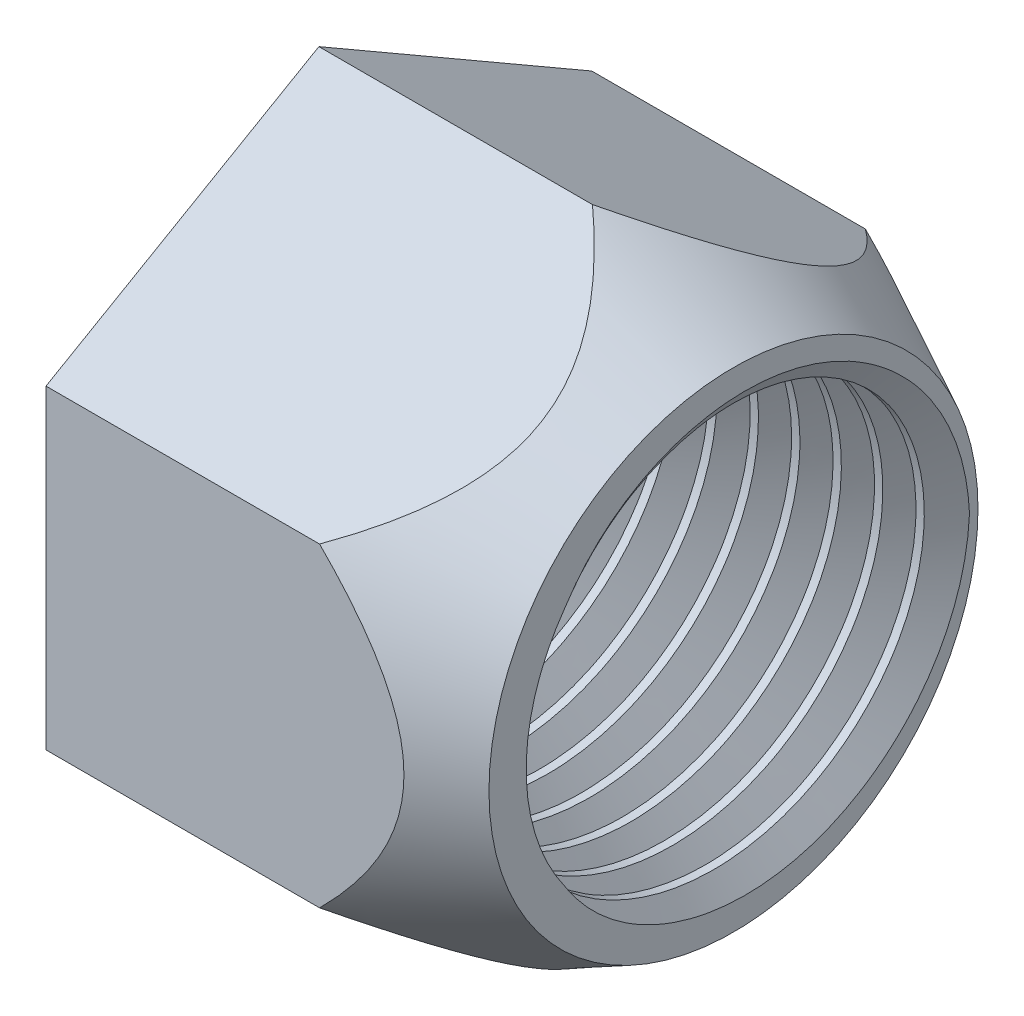
SolidWorks part; units mm, degrees
material "AISI 316 Annealed Stainless Steel Bar (SS)"
ref_plane "Front Plane" through (0, 0, 0) normal (0, 0, 1) x (1, 0, 0)
ref_plane "Top Plane" through (0, 0, 0) normal (0, 1, 0) x (1, 0, 0)
ref_plane "Right Plane" through (0, 0, 0) normal (1, 0, 0) x (0, 0, -1)
sketch "Sketch1" plane through (0, 0, 0) normal (1, 0, 0) x (0, 0, -1)
  line L1 (0, 3.8) -> (-3.2909, 1.9)
  line L2 (-3.2909, 1.9) -> (-3.2909, -1.9)
  line L3 (-3.2909, -1.9) -> (0, -3.8)
  line L4 (0, -3.8) -> (3.2909, -1.9)
  line L5 (3.2909, -1.9) -> (3.2909, 1.9)
  line L6 (3.2909, 1.9) -> (0, 3.8)
  circle A0 centre (0, 0) radius 2.5
  circle A1 centre (0, 0) radius 3.2909 construction
  dimension "D1" = 5
extrude "Boss-Extrude1" add sketch "Sketch1" along normal blind 5
sketch3d "3DSketch2"
  line L0 (5, 3.8, 0) -> (0, 3.8, 0) construction
  line L1 (5, -3.8, 0) -> (0, -3.8, 0) construction
  line L3 (3.2995, 3.8, 0) -> (5, 2.9489, 0)
  line L5 (4, 4.0725, 0) -> (5.8158, 4.0725, 0)
  line L6 (5.8158, 4.0725, 0) -> (5.8158, 2.9489, 0)
  line L8 (5, 2.9489, 0) -> (5.8158, 2.9489, 0)
  line L9 (3.2995, 3.8, 0) -> (3.2995, 4.0725, 0)
  line L10 (3.2995, 4.0725, 0) -> (4, 4.0725, 0)
sketch "Sketch3" plane through (0, 0, 0) normal (0, 0, 1) x (1, 0, 0)
  line L0 (0, 0) -> (8.766, 0) construction
revolve "Cut-Revolve5" cut sketch "3DSketch2" angle 360 about L0
sketch "Sketch4" plane through (0, 0, 0) normal (-1, 0, 0) x (0, 0, 1)
  line L0 (0, 0) -> (-2.5, 0) construction
  circle A0 centre (0, 0) radius 2.5 construction
sketch3d "3DSketch3"
  point P0 (0, 0, -2.5)
sketch "Sketch5" plane through (0, 0, 0) normal (-1, 0, 0) x (0, 0, 1)
  circle A0 centre (0, 0) radius 2.5 construction
  circle A1 centre (0, 0) radius 2.5
curve "Helix/Spiral1" pitch 0.5 height 5 radius 2.5 centre (0, 0, 0) axis (1, 0, 0) start towards (0, 0, 1)
sketch3d "3DSketch4"
  line L0 (0, 0, -2.5) -> (0, 0, -3.1741) construction
  line L1 (0.2, 0, -2.5) -> (-0.2, 0, -2.5)
  line L2 (-0.2, 0, -2.5) -> (0, 0, -2.8464)
  line L3 (0.2, 0, -2.5) -> (0, 0, -2.8464)
  dimension "D1" = 0.2
  dimension "D2" = 0.4
sweep "Cut-Sweep1" cut profiles "3DSketch4" path "Helix/Spiral1" align with end faces yes
sketch3d "3DSketch5"
  line L0 (0, 0, 0) -> (8.766, 0, 0) construction
